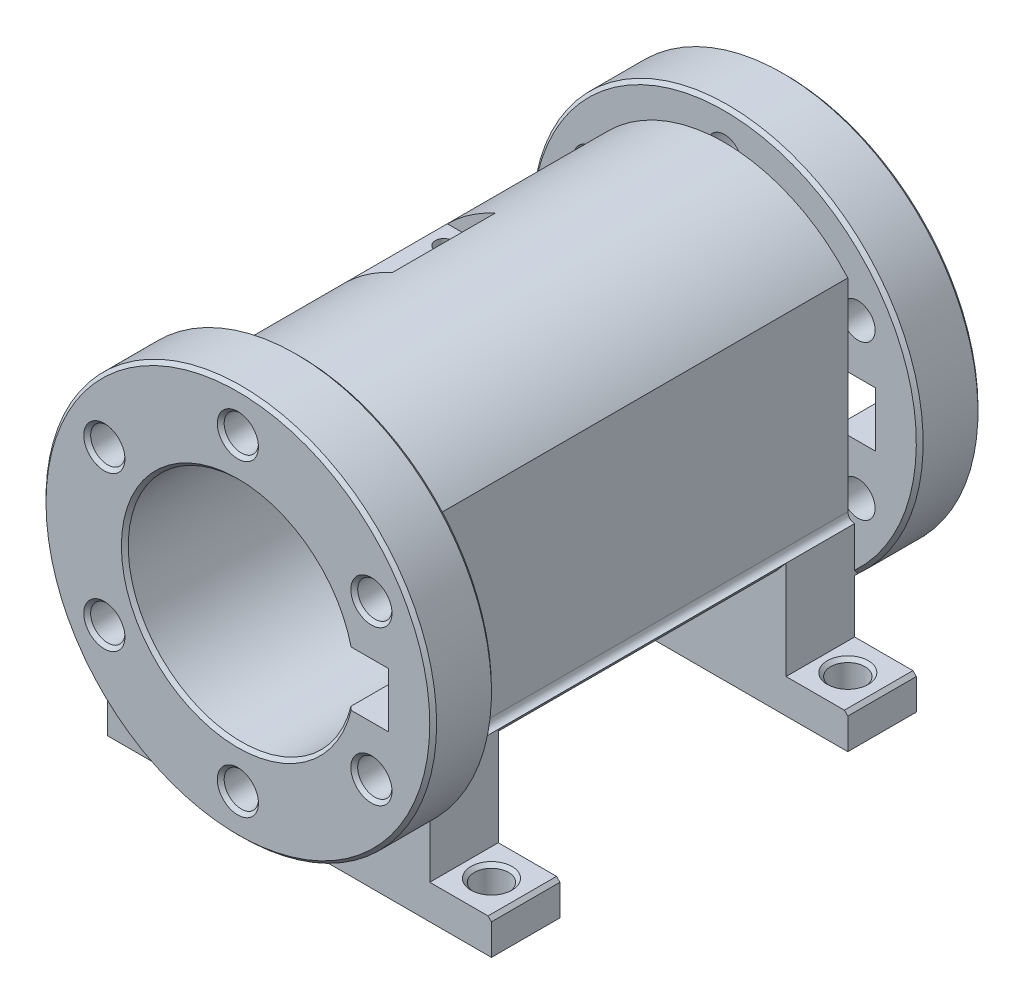
SolidWorks part; units mm, degrees
ref_plane "Front Plane" through (0, 0, 0) normal (0, 0, 1) x (1, 0, 0)
ref_plane "Top Plane" through (0, 0, 0) normal (0, 1, 0) x (1, 0, 0)
ref_plane "Right Plane" through (0, 0, 0) normal (1, 0, 0) x (0, 0, -1)
sketch "Sketch1" plane through (0, 0, 0) normal (0, 0, 1) x (1, 0, 0)
  circle A0 centre (0, 0) radius 28.5
  dimension "D1" = 57
extrude "Boss-Extrude1" add sketch "Sketch1" along normal blind 9
sketch "Sketch2" plane through (0, 0, 0) normal (0, 0, 1) x (1, 0, 0)
  line L0 (18, 15.8745) -> (18, -15.8745)
  arc A0 (18, 15.8745) -> (18, -15.8745) centre (0, 0) ccw
  point P5 (18, 0)
  dimension "D1" = 48
  dimension "D2" = 18
extrude "Boss-Extrude2" add sketch "Sketch2" against normal blind 62
sketch "Sketch3" plane through (0, 0, -62) normal (0, 0, -1) x (-1, 0, 0)
  circle A0 centre (0, 0) radius 28.5 construction
  circle A1 centre (0, 0) radius 28.5
extrude "Boss-Extrude3" add sketch "Sketch3" along normal blind 9
sketch "Sketch4" plane through (0, 0, 9) normal (0, 0, 1) x (1, 0, 0)
  circle A0 centre (0, 0) radius 22.5 construction
  circle A1 centre (0, 22.5) radius 2.5
  circle A2 centre (19.4856, 11.25) radius 2.5
  circle A3 centre (19.4856, -11.25) radius 2.5
  circle A4 centre (0, -22.5) radius 2.5
  circle A5 centre (-19.4856, -11.25) radius 2.5
  circle A6 centre (-19.4856, 11.25) radius 2.5
  point P18 (0, 0)
  dimension "D1" = 45
  dimension "D2" = 5
  dimension "D3" = 6
extrude "Cut-Extrude1" cut sketch "Sketch4" against normal blind 9
sketch "Sketch5" plane through (0, 0, 9) normal (0, 0, 1) x (1, 0, 0)
  circle A0 centre (0, 0) radius 16.5
  dimension "D1" = 33
extrude "Cut-Extrude2" cut sketch "Sketch5" against normal through all
sketch "Sketch7" plane through (0, 0, 9) normal (0, 0, 1) x (1, 0, 0)
  line L1 (16.0078, 4) -> (22.0078, 4)
  line L2 (16.0078, 4) -> (16.0078, -4)
  line L3 (16.0078, -4) -> (22.0078, -4)
  line L4 (22.0078, 4) -> (22.0078, -4)
  circle A0 centre (0, 0) radius 16.5 construction
  circle A1 centre (0, 0) radius 16.5
  point P7 (16.0078, 0)
  circle M1 centre (0, 0) radius 16.5
  dimension "D1" = 8
  dimension "D2" = 6
extrude "Cut-Extrude4" cut sketch "Sketch7" against normal blind 9 contours L4 L1 L3 M1 region at (19.1705, 0, 9)
sketch "Sketch8" plane through (0, 0, 0) normal (0, 0, 1) x (1, 0, 0)
  line L0 (-19, -29) -> (-19, -14.6629)
  line L1 (28, -34) -> (-28, -34)
  line L2 (28, -34) -> (28, -29)
  line L3 (28, -29) -> (19, -29)
  line L4 (-28, -34) -> (-28, -29)
  line L5 (28, -34) -> (-13.7878, -30.2689) construction
  line L6 (28, -29) -> (-28, -34) construction
  line L7 (19, -29) -> (19, -14.6629)
  line L8 (-19, -29) -> (-28, -29)
  arc A1 (18, 15.8745) -> (2.0637, 23.9111) centre (0, 0) ccw construction
  arc A2 (-19, -14.6629) -> (19, -14.6629) centre (0, 0) ccw
  point P0 (0, -31.5)
  dimension "D1" = 5
  dimension "D2" = 34
  dimension "D3" = 19
  dimension "D4" = 9
  dimension "D5" = 19
extrude "Boss-Extrude4" add sketch "Sketch8" against normal up to surface (62 mm away) up to face at (-3, 0, -62)
sketch "Sketch9" plane through (0, 0, -71) normal (0, 0, -1) x (-1, 0, 0)
  circle A1 centre (19.4856, -11.25) radius 2.5
  circle A2 centre (19.4856, -11.25) radius 2.5
  circle A3 centre (0, -22.5) radius 2.5
  circle A4 centre (0, -22.5) radius 2.5
  circle A5 centre (-19.4856, -11.25) radius 2.5
  circle A6 centre (-19.4856, -11.25) radius 2.5
  circle A7 centre (-19.4856, 11.25) radius 2.5
  circle A8 centre (-19.4856, 11.25) radius 2.5
  circle A9 centre (0, 22.5) radius 2.5
  circle A10 centre (0, 22.5) radius 2.5
  circle A11 centre (19.4856, 11.25) radius 2.5
  circle A12 centre (19.4856, 11.25) radius 2.5
  dimension "D1" = 0
  dimension "D2" = 0
  dimension "D3" = 0
  dimension "D4" = 0
  dimension "D5" = 0
  dimension "D6" = 0
extrude "Cut-Extrude5" cut sketch "Sketch9" against normal blind 9
sketch "Sketch10" plane through (0, -29, 0) normal (0, 1, 0) x (1, 0, 0)
  line L0 (28, 62) -> (28, 0) construction
  line L1 (0, -9) -> (0, 71) construction
  line L2 (-28.5, -9) -> (28.5, -9) construction
  line L3 (28.5, 71) -> (-28.5, 71) construction
  circle A0 centre (23, 57) radius 2.5
  circle A1 centre (23, 5) radius 2.5
  circle A2 centre (-23, 5) radius 2.5
  circle A3 centre (-23, 57) radius 2.5
  point P8 (28, 31)
  dimension "D1" = 5
  dimension "D2" = 5
  dimension "D3" = 23
  dimension "D4" = 26
  dimension "D5" = 26
extrude "Cut-Extrude6" cut sketch "Sketch10" against normal blind 9
sketch "Sketch11" plane through (0, -29, 0) normal (0, 1, 0) x (1, 0, 0)
  line L0 (-24, 62) -> (-24, 0) construction
  line L1 (-24, 38.5) -> (-17, 38.5)
  line L2 (-24, 38.5) -> (-24, 23.5)
  line L3 (-24, 23.5) -> (-17, 23.5)
  line L4 (-17, 38.5) -> (-17, 23.5)
  line L5 (-28, 31) -> (28, 31) construction
  line L6 (-28, 62) -> (-28, 0) construction
  line L7 (28, 62) -> (28, 0) construction
  point P12 (-17, 31)
  dimension "D1" = 7.5
  dimension "D2" = 7.5
  dimension "D3" = 7
chamfer "Chamfer1" distance 0.5 angle 45 24 edges at (2.5, -22.5, 9) (-23, -29, -7.5) (-28, -29, -31) (-23, -29, -59.5) (28, -29, -31) (23, -29, -54.5) (23, -29, -2.5) (-16.5, 0, 9) (16.5, 0, -71) (0, 28.5, -62) (-28.5, 0, -71) (16.9856, 11.25, -71) (-2.5, 22.5, -71) (-21.9856, 11.25, -71) (-21.9856, -11.25, -71) (-2.5, -22.5, -71) (16.9856, -11.25, -71) (0, 28.5, 0) (28.5, 0, 9) (-16.9856, -11.25, 9) (21.9856, -11.25, 9) (21.9856, 11.25, 9) (-16.9856, 11.25, 9) (2.5, 22.5, 9)
fillet "Fillet1" radius 1 2 edges at (-19, -14.6629, -31) (18, -15.8745, -31)
ref_plane "Plane1" through (0, 0, -31) normal (0, 0, 1) x (1, 0, 0)
sketch "Sketch12" plane through (0, 0, -31) normal (0, 0, 1) x (1, 0, 0)
  line L3 (-9.941, 23.074) -> (-9.941, 17)
  line L4 (-9.941, 17) -> (-16.941, 17)
  arc A1 (-16.941, 17) -> (-9.941, 23.074) centre (-8.7641, 14.6472) cw
  dimension "D3" = 7
  dimension "D1" = 17
  dimension "D2" = 9.941
extrude "Cut-Extrude7" cut sketch "Sketch12" against normal mid plane 15
sketch "Sketch13" plane through (0, 17, 0) normal (0, 1, 0) x (1, 0, 0)
  line L0 (-28, 31) -> (28, 31) construction
  line L3 (-9.941, 38.5) -> (-9.941, 23.5) construction
  line L4 (-9.941, 23.5) -> (-9.941, 38.5) construction
  circle A0 centre (-14.441, 35.5) radius 1.25
  circle A1 centre (-14.441, 26.5) radius 1.25
  dimension "D1" = 2.5
  dimension "D2" = 2.5
  dimension "D3" = 4.5
  dimension "D4" = 4.5
  dimension "D5" = 4.5
  dimension "D6" = 4.5
extrude "Cut-Extrude8" cut sketch "Sketch13" against normal blind 6
sketch "Sketch15" plane through (0, 0, -31) normal (0, 0, 1) x (1, 0, 0)
  line L0 (-19, -29) -> (-19, -14.6629)
  line L1 (-28, -34) -> (28, -34) construction
  line L2 (-19, -34) -> (19, -34)
  line L3 (19, -29) -> (19, -14.6629)
  line L4 (28, -34) -> (28, -29.5) construction
  line L5 (-19, -29) -> (-28, -29)
  line L7 (-19, -34) -> (-28, -34)
  line L8 (-28, -29) -> (-28, -34)
  line L9 (19, -29) -> (28, -29)
  line L11 (19, -34) -> (28, -34)
  line L12 (28, -29) -> (28, -34)
  arc A0 (-19.6758, 13.7428) -> (-21.7395, 10.1684) centre (0, 0) ccw construction
  arc A1 (-19, -14.6629) -> (19, -14.6629) centre (0, 0) ccw
extrude "Cut-Extrude10" cut sketch "Sketch15" against normal mid plane 42 contours L5 L8 L7 L2 L11 L12 L9 L3 A1 L0
mirror "Mirror1" about plane through (0, 0, -31) normal (0, 0, 1) of "Cut-Extrude4"
